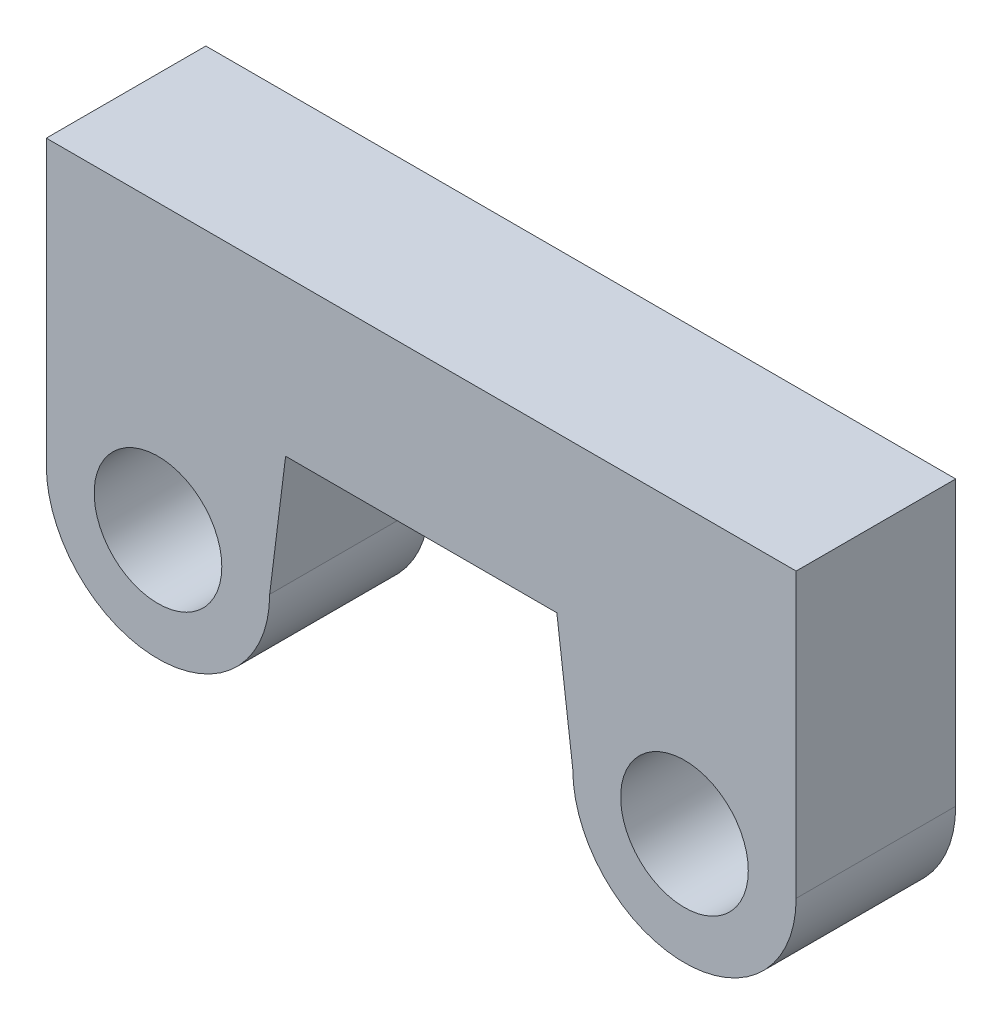
SolidWorks part; units mm, degrees
material "ABS"
ref_plane "Plano frontal" through (0, 0, 0) normal (0, 0, 1) x (1, 0, 0)
ref_plane "Plano superior" through (0, 0, 0) normal (0, 1, 0) x (1, 0, 0)
ref_plane "Plano direito" through (0, 0, 0) normal (1, 0, 0) x (0, 0, -1)
sketch "Esboço1" plane through (0, 0, 0) normal (0, 0, 1) x (1, 0, 0)
  line L0 (-16.5, 0) -> (16.5, 0) construction
  line L1 (-23.5, 0) -> (-23.5, 17.7669)
  line L2 (-9.5, 0) -> (-8.5, 8)
  line L3 (-8.5, 8) -> (8.5, 8)
  line L4 (8.5, 8) -> (9.5, 0)
  line L5 (-23.5, 17.7669) -> (23.5, 17.7669)
  line L6 (23.5, 17.7669) -> (23.5, 0)
  arc A0 (-23.5, 0) -> (-9.5, 0) centre (-16.5, 0) ccw
  arc A1 (9.5, 0) -> (23.5, 0) centre (16.5, 0) ccw
  circle A2 centre (-16.5, 0) radius 4
  circle A3 centre (16.5, 0) radius 4
  point P4 (0, 0)
  dimension "D1" = 8
  dimension "D2" = 8
  dimension "D4" = 8
  dimension "D3" = 33
  dimension "D6" = 14
  dimension "D7" = 14
  dimension "D8" = 8
  dimension "D5" = 8
extrude "Ressalto-extrusão1" add sketch "Esboço1" along normal blind 10
